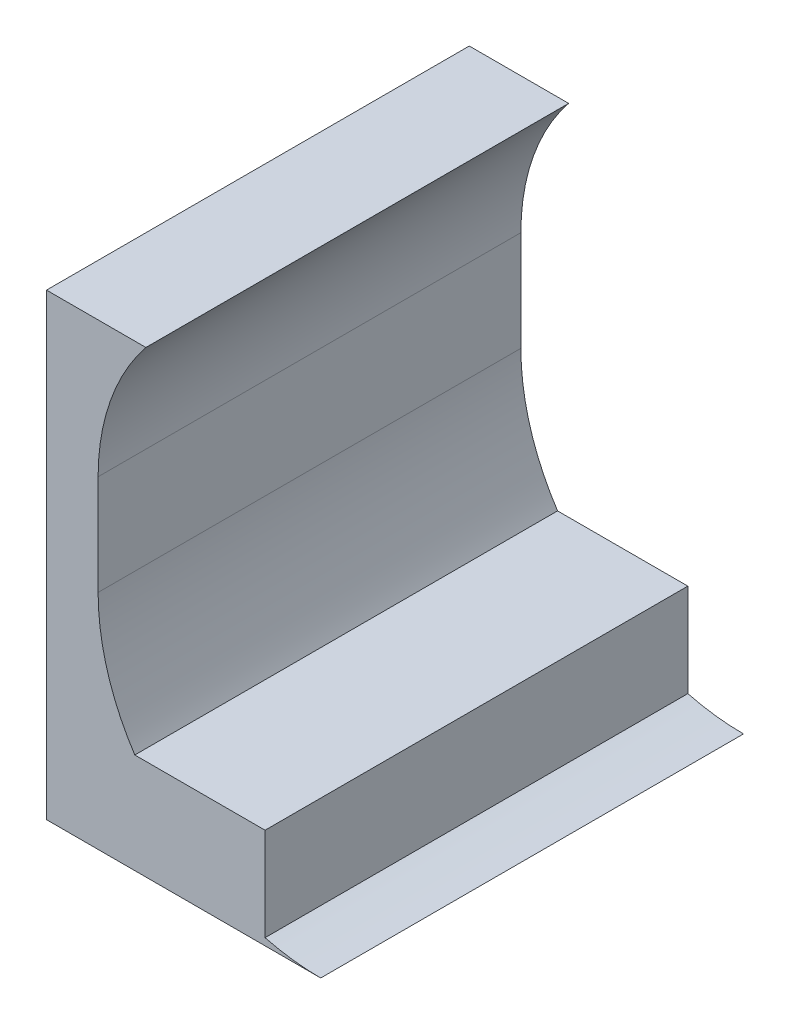
SolidWorks part; units mm, degrees
ref_plane "Front Plane" through (0, 0, 0) normal (0, 0, 1) x (1, 0, 0)
ref_plane "Top Plane" through (0, 0, 0) normal (0, 1, 0) x (1, 0, 0)
ref_plane "Right Plane" through (0, 0, 0) normal (1, 0, 0) x (0, 0, -1)
sketch "Sketch3" plane through (0, 0, 0) normal (0, 0, 1) x (1, 0, 0)
  line L0 (-19.5, 0) -> (-19.5, -9) construction
  line L1 (-19.5, 0) -> (-19.5, -9)
  line L2 (-4.5, -20) -> (-16.2033, -20)
  line L3 (-15.2085, 12.2046) -> (-24.1359, 12.2046)
  line L4 (0.5, -29) -> (-24.1359, -29)
  line L5 (-24.1359, -29) -> (-24.1359, 12.2046)
  line L6 (-4.5, -20) -> (-4.5, -28.3649)
  arc A0 (-4.5, -28.3649) -> (0.5, -29) centre (0.5, -9) ccw construction
  arc A1 (-4.5, -28.3649) -> (0.5, -29) centre (0.5, -9) ccw
  arc A2 (-15.2085, 12.2046) -> (-19.5, 0) centre (0, 0) ccw construction
  arc A3 (-19.5, -9) -> (-4.5, -28.3649) centre (0.5, -9) ccw construction
  arc A4 (-15.2085, 12.2046) -> (-19.5, 0) centre (0, 0) ccw
  arc A5 (-19.5, -9) -> (-16.2033, -20) centre (0.5, -9) ccw
extrude "Boss-Extrude1" add sketch "Sketch3" against normal up to surface (37.9817 mm away)
